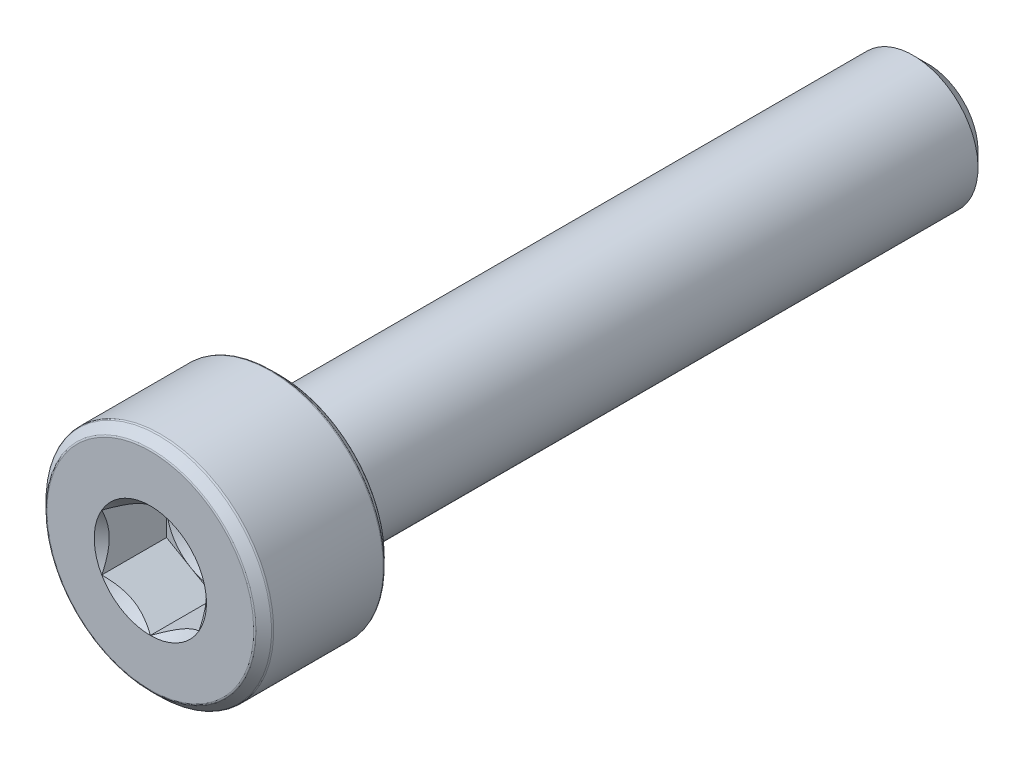
SolidWorks part; units mm, degrees
material "Alloy Steel (SS)"
ref_plane "Front Plane" through (0, 0, 0) normal (0, 0, 1) x (1, 0, 0)
ref_plane "Top Plane" through (0, 0, 0) normal (0, 1, 0) x (1, 0, 0)
ref_plane "Right Plane" through (0, 0, 0) normal (1, 0, 0) x (0, 0, -1)
sketch "Sketch1" plane through (0, 0, 0) normal (1, 0, 0) x (0, 0, -1)
  line L0 (-12, 0) -> (12, 0) construction
  line L1 (-12, 0) -> (-12, 3.5)
  line L2 (-12, 3.5) -> (-8, 3.5)
  line L3 (-8, 3.5) -> (-8, 2)
  line L4 (-8, 2) -> (11.5453, 2)
  line L5 (11.9563, 2.0758) -> (12.3063, 1.4696) construction
  line L6 (12.3063, 1.4696) -> (12.6563, 2.0758) construction
  line L7 (12.6563, 2.0758) -> (11.9563, 2.0758) construction
  line L8 (11.5453, 2) -> (12, 1.5453)
  line L9 (12, 1.5453) -> (12, 0)
  line L10 (12, 2) -> (12.6125, 2) construction
  line L11 (12.3062, 2.0758) -> (12.3063, 2) construction
  line L12 (12.3063, 2) -> (12.3063, 1.5453) construction
  line L13 (12.3063, 1.5453) -> (12.3063, 1.4696) construction
  line L14 (12.2625, 1.5453) -> (12.35, 1.5453)
  line L15 (11.9781, 2.0379) -> (12.6344, 2.0379)
  line L16 (12.35, 1.5453) -> (12.6344, 2.0379)
  line L17 (12.2625, 1.5453) -> (11.9781, 2.0379)
  line L18 (-12, 1.5) -> (-10, 1.5)
  line L19 (-10, 1.5) -> (-10, 0)
  line L20 (9.55, 2) -> (9.55, -2) construction
  point P20 (12.3063, 2.0379)
  point P22 (9.55, -2)
  point P28 (9.55, 0)
  point P29 (11.5453, -2)
  dimension "Head Diameter" = 7
  dimension "Length" = 20
  dimension "Head Height" = 4
  dimension "D2" = 4
  dimension "D1" = 45
  dimension "Thread Pitch" = 0.7
  dimension "D3" = 0.0875
  dimension "Drive Size" = 3
  dimension "D4" = 2.45
  dimension "D5" = 2
sketch "Sketch3" plane through (0, 0, 0) normal (1, 0, 0) x (0, 0, -1)
  line L0 (-12, 3.191) -> (-12, 1.5)
  line L1 (-12, 1.5) -> (-10, 1.5)
  line L2 (-10, 1.5) -> (-10, 0)
  line L3 (-10, 0) -> (12, 0)
  line L4 (12, 0) -> (12, 1.5453)
  line L5 (12, 1.5453) -> (11.5453, 2)
  line L6 (11.5453, 2) -> (-8, 2)
  line L7 (-8, 2) -> (-8, 3.191)
  line L8 (-8.309, 3.5) -> (-11.691, 3.5)
  line L9 (-11.9795, 3.2405) -> (-11.7405, 3.4795)
  line L10 (-8.2595, 3.4795) -> (-8.0205, 3.2405)
  line L11 (-12, 3.5) -> (-8, 3.5) construction
  arc A0 (-8.0205, 3.2405) -> (-8, 3.191) centre (-8.07, 3.191) cw
  arc A1 (-8.2595, 3.4795) -> (-8.309, 3.5) centre (-8.309, 3.43) ccw
  arc A2 (-11.7405, 3.4795) -> (-11.691, 3.5) centre (-11.691, 3.43) cw
  arc A3 (-11.9795, 3.2405) -> (-12, 3.191) centre (-11.93, 3.191) ccw
  point P29 (-12, 3.22)
  dimension "D3" = 0.07
  dimension "D1" = 45
  dimension "D2" = 0.28
revolve "Revolve1" add sketch "Sketch3" angle 360 about L0
sketch "Sketch4" plane through (0, 0, 12) normal (0, 0, 1) x (1, 0, 0)
  line L1 (0, 1.7321) -> (-1.5, 0.866)
  line L2 (-1.5, 0.866) -> (-1.5, -0.866)
  line L3 (-1.5, -0.866) -> (0, -1.7321)
  line L4 (0, -1.7321) -> (1.5, -0.866)
  line L5 (1.5, -0.866) -> (1.5, 0.866)
  line L6 (1.5, 0.866) -> (0, 1.7321)
  circle A0 centre (0, 0) radius 1.5 construction
extrude "Cut-Extrude1" cut sketch "Sketch4" against normal up to vertex (2 mm away) up to point (0, 1.5, 10)
sketch "Sketch5" plane through (0, 0, 12) normal (0, 0, 1) x (1, 0, 0)
  circle A0 centre (0, 0) radius 1.7321
extrude "Cut-Extrude2" cut sketch "Sketch5" against normal up to next (2 mm away) draft 45
sketch "Sketch10" plane through (0, 0, 10) normal (0, 0, 1) x (1, 0, 0)
  line L0 (1.5, 0.866) -> (1.5, -0.866) construction
  circle A0 centre (0, 0) radius 1.5
extrude "Cut-Extrude3" cut sketch "Sketch10" against normal through all draft 60
split "Split1" [suppressed] bodies to split 112
sketch "Sketch6" [suppressed] plane through (0, 0, -12) normal (0, 0, -1) x (-1, 0, 0)
  circle A0 centre (0, 0) radius 2 construction
  circle A1 centre (0, 0) radius 2
curve "Helix/Spiral1" [suppressed] pitch 0.7 height 20.7 turns 29.5714
sketch "Sketch7" [suppressed] plane through (0, 0, 0) normal (1, 0, 0) x (0, 0, -1)
  line L0 (12.2625, 1.5453) -> (12.35, 1.5453) construction
  line L1 (12.2625, 1.5453) -> (11.9781, 2.0379) construction
  line L2 (11.9781, 2.0379) -> (12.6344, 2.0379) construction
  line L3 (12.35, 1.5453) -> (12.6344, 2.0379) construction
  line L4 (12.2625, 1.5453) -> (12.35, 1.5453)
  line L5 (12.2625, 1.5453) -> (11.9781, 2.0379)
  line L6 (11.9781, 2.0379) -> (12.6344, 2.0379)
  line L7 (12.35, 1.5453) -> (12.6344, 2.0379)
sweep "Cut-Sweep1" [suppressed] cut profiles "Sketch7" path "Helix/Spiral1"
sketch "Sketch11" [suppressed] plane through (0, 0, 0) normal (1, 0, 0) x (0, 0, -1)
  line L0 (-8, 2.175) -> (-7.825, 2) construction
  line L1 (-8, 3.5) -> (-8, 2) construction
  line L2 (-8, 2) -> (11.5453, 2) construction
  line L3 (-7.825, 2) -> (-7.3, 2)
  line L4 (-7.3, 2) -> (-5.3, 0)
  line L5 (-12, 0) -> (12, 0) construction
  line L6 (-5.3, 0) -> (-8, 0)
  line L7 (-8, 0) -> (-8, 2.175)
  line L8 (-8, -3.22) -> (-8, 3.22) construction
  arc A0 (-7.825, 2) -> (-8, 2.175) centre (-7.825, 2.175) cw
  dimension "D4" = 0.7
  dimension "D1" = 45
  dimension "D2" = 0.175
  dimension "D3" = 45
revolve "Revolve2" [suppressed] add sketch "Sketch11" angle 360 about L6
sketch "Sketch12" [suppressed] plane through (0, 0, 12) normal (0, 0, 1) x (1, 0, 0)
  line L0 (0, 0) -> (0, 3.5) construction
  line L1 (0, 0) -> (0.175, 3.7027) construction
  line L2 (0.175, 3.7027) -> (-0.175, 3.7027)
  line L3 (-0.175, 3.7027) -> (0, 0) construction
  line L4 (-0.175, 3.7027) -> (-0.0077, 3.3953)
  line L5 (0.0077, 3.3953) -> (0.175, 3.7027)
  line L7 (0, 3.191) -> (0, 3.2405) construction
  circle A0 centre (0, 0) radius 3.5 construction
  arc A2 (-0.0077, 3.3953) -> (0.0077, 3.3953) centre (0, 3.3995) ccw
  point P11 (0, 3.3812)
  point P13 (0, 3.2158)
  point P15 (0, 3.3908)
  dimension "D3" = 0.0087
  dimension "D1" = 0.35
  dimension "D2" = 5.412
  dimension "D4" = 0.175
extrude "Cut-Extrude4" [suppressed] cut sketch "Sketch12" against normal up to vertex
sketch "Sketch13" [suppressed] plane through (0, 0, 10) normal (0, 0, 1) x (1, 0, 0)
  circle A0 centre (0, 0) radius 3.5
  circle A2 centre (0, 0) radius 2
  arc A3 (0.0643, 3.4994) -> (-0.0643, 3.4994) centre (0, 0) ccw construction
extrude "Boss-Extrude1" [suppressed] add sketch "Sketch13" along normal through all draft 45
fillet "Fillet1" [suppressed] radius 0.0125
pattern_circular "CirPattern1" [suppressed] count 98 over 360 of bodies 116
equation "\"D3@Sketch1\" = \"Thread Pitch@Sketch1\" / 8"
equation "\"D4@Sketch1\" = \"Thread Pitch@Sketch1\" * 3.5"
equation "\"D3@Helix/Spiral1\" = \"Length@Sketch1\" + \"Thread Pitch@Sketch1\""
equation "\"D4@Helix/Spiral1\" = \"Thread Pitch@Sketch1\""
equation "\"D5@Sketch1\"=\"Head Height@Sketch1\"*0.5"
equation "\"D2@Sketch3\"=\"Head Diameter@Sketch1\" /25"
equation "\"D2@Sketch11\"=\"Thread Pitch@Sketch1\" / 4"
equation "\"D1@Sketch12\"=\"Head Diameter@Sketch1\"*0.05"
equation "\"D1@CirPattern1\"=int(360/(\"D2@Sketch12\"*.675))"
equation "\"D3@Sketch12\"=\"D1@Sketch12\"*00.025"
equation "\"D4@Sketch11\"=\"Thread Pitch@Sketch1\" "
equation "\"D3@Sketch3\"=\"D2@Sketch3\"*0.25"
equation "\"D4@Sketch12\"= \"D2@Sketch3\"*0.625"
